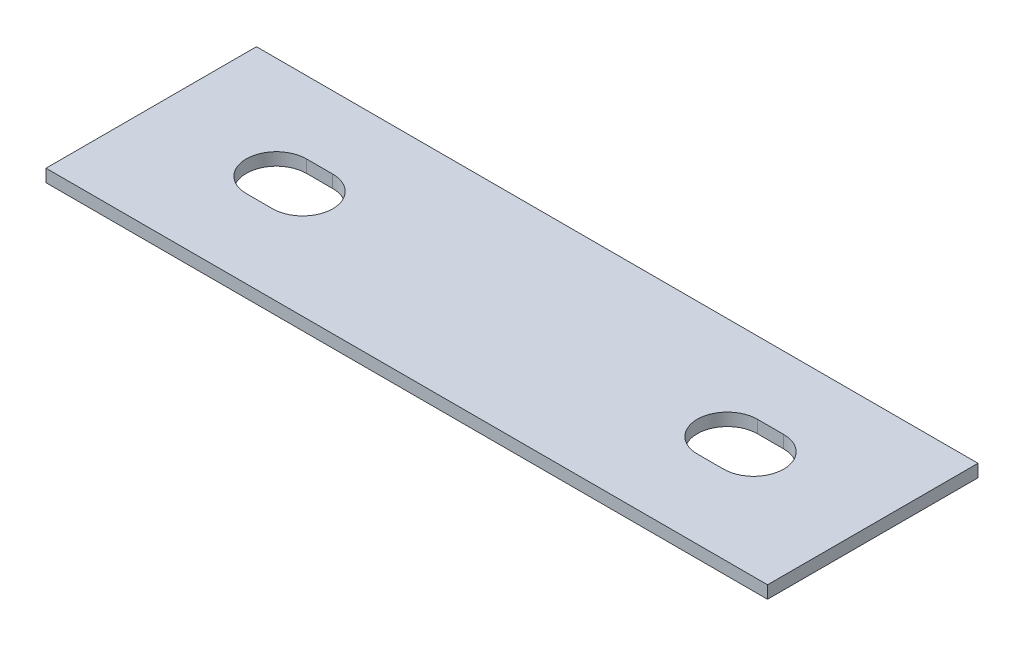
SolidWorks part; units mm, degrees
material "Plain Carbon Steel"
ref_plane "Front Plane" through (0, 0, 0) normal (0, 0, 1) x (1, 0, 0)
ref_plane "Top Plane" through (0, 0, 0) normal (0, 1, 0) x (1, 0, 0)
ref_plane "Right Plane" through (0, 0, 0) normal (1, 0, 0) x (0, 0, -1)
sketch "Sketch1" plane through (0, 0, 0) normal (0, 1, 0) x (1, 0, 0)
  line L1 (0, 0) -> (152.4, 0)
  line L2 (0, 0) -> (0, 44.45)
  line L3 (0, 44.45) -> (152.4, 44.45)
  line L4 (152.4, 0) -> (152.4, 44.45)
  dimension "D1" = 152.4
  dimension "D2" = 44.45
base flange "Base-Flange1" sketch "Sketch1" thickness 2.6568 reverse thickness direction no parameters "D1"=3.175
sketch "Sketch10" plane through (0, -2.6568, 0) normal (0, -1, 0) x (1, 0, 0)
  line L0 (25.7969, -29.21) -> (31.3531, -29.21) construction
  line L1 (31.3531, -16.51) -> (25.7969, -16.51) construction
  line L2 (121.0469, -29.21) -> (126.6031, -29.21) construction
  line L3 (126.6031, -16.51) -> (121.0469, -16.51) construction
  line L12 (25.7969, -29.21) -> (31.3531, -29.21)
  line L13 (31.3531, -16.51) -> (25.7969, -16.51)
  line L14 (121.0469, -29.21) -> (126.6031, -29.21)
  line L15 (126.6031, -16.51) -> (121.0469, -16.51)
  arc A0 (25.7969, -16.51) -> (25.7969, -29.21) centre (25.7969, -22.86) ccw construction
  arc A1 (31.3531, -29.21) -> (31.3531, -16.51) centre (31.3531, -22.86) ccw construction
  arc A2 (121.0469, -16.51) -> (121.0469, -29.21) centre (121.0469, -22.86) ccw construction
  arc A3 (126.6031, -29.21) -> (126.6031, -16.51) centre (126.6031, -22.86) ccw construction
  arc A4 (25.7969, -16.51) -> (25.7969, -29.21) centre (25.7969, -22.86) ccw
  arc A5 (31.3531, -29.21) -> (31.3531, -16.51) centre (31.3531, -22.86) ccw
  arc A6 (121.0469, -16.51) -> (121.0469, -29.21) centre (121.0469, -22.86) ccw
  arc A7 (126.6031, -29.21) -> (126.6031, -16.51) centre (126.6031, -22.86) ccw
extrude "Cut-Extrude3" cut sketch "Sketch10" against normal through all normal cut yes
sketch "Bend-Lines1" [suppressed] plane through (0, 0, 0) normal (0, 1, 0) x (1, 0, 0)
sketch "Bounding-Box1" [suppressed] plane through (0, 0, 0) normal (0, 1, 0) x (1, 0, 0)
sheet metal parameters "Sheet-Metal1" thickness 2.6568 parameters "D1"=3.175
flat pattern "Flat-Pattern1" [suppressed]
sketch "Bend-Lines2" plane through (0, 0, 0) normal (0, 1, 0) x (1, 0, 0)
sketch3d "Bounding-Box2" [suppressed]
  line L0 (152.4, 44.45, 0) -> (0, 44.45, 0) construction
  line L1 (152.4, 0, 0) -> (0, 0, 0) construction
  line L2 (152.4, 44.45, 0) -> (152.4, 0, 0) construction
  line L3 (0, 44.45, 0) -> (0, 0, 0) construction
sketch "Sketch10-1" [suppressed] plane through (0, -2.6568, 0) normal (0, -1, 0) x (1, 0, 0)
  line L8 (0, 0) -> (0, -44.45)
  line L9 (0, -44.45) -> (152.4, -44.45)
  line L10 (152.4, -44.45) -> (152.4, 0)
  line L11 (152.4, 0) -> (0, 0)
  line L12 (25.7969, -29.21) -> (31.3531, -29.21)
  line L13 (31.3531, -16.51) -> (25.7969, -16.51)
  line L14 (121.0469, -29.21) -> (126.6031, -29.21)
  line L15 (126.6031, -16.51) -> (121.0469, -16.51)
  arc A4 (25.7969, -16.51) -> (25.7969, -29.21) centre (25.7969, -22.86) ccw
  arc A5 (31.3531, -29.21) -> (31.3531, -16.51) centre (31.3531, -22.86) ccw
  arc A6 (121.0469, -16.51) -> (121.0469, -29.21) centre (121.0469, -22.86) ccw
  arc A7 (126.6031, -29.21) -> (126.6031, -16.51) centre (126.6031, -22.86) ccw
sheet metal parameters "Sheet-Metal6" thickness 2.6568 parameters "D1"=3.175
flat pattern "Flat-Pattern1" [suppressed]
sketch "Bend-Lines2" plane through (0, 0, 0) normal (0, 1, 0) x (1, 0, 0)
sketch3d "Bounding-Box2" [suppressed]
  line L0 (152.4, 44.45, 0) -> (0, 44.45, 0) construction
  line L1 (152.4, 0, 0) -> (0, 0, 0) construction
  line L2 (152.4, 44.45, 0) -> (152.4, 0, 0) construction
  line L3 (0, 44.45, 0) -> (0, 0, 0) construction
sketch "Sketch10-1" [suppressed] plane through (0, -2.6568, 0) normal (0, -1, 0) x (1, 0, 0)
  line L12 (25.7969, -29.21) -> (31.3531, -29.21)
  line L13 (31.3531, -16.51) -> (25.7969, -16.51)
  line L14 (121.0469, -29.21) -> (126.6031, -29.21)
  line L15 (126.6031, -16.51) -> (121.0469, -16.51)
  arc A4 (25.7969, -16.51) -> (25.7969, -29.21) centre (25.7969, -22.86) ccw
  arc A5 (31.3531, -29.21) -> (31.3531, -16.51) centre (31.3531, -22.86) ccw
  arc A6 (121.0469, -16.51) -> (121.0469, -29.21) centre (121.0469, -22.86) ccw
  arc A7 (126.6031, -29.21) -> (126.6031, -16.51) centre (126.6031, -22.86) ccw
